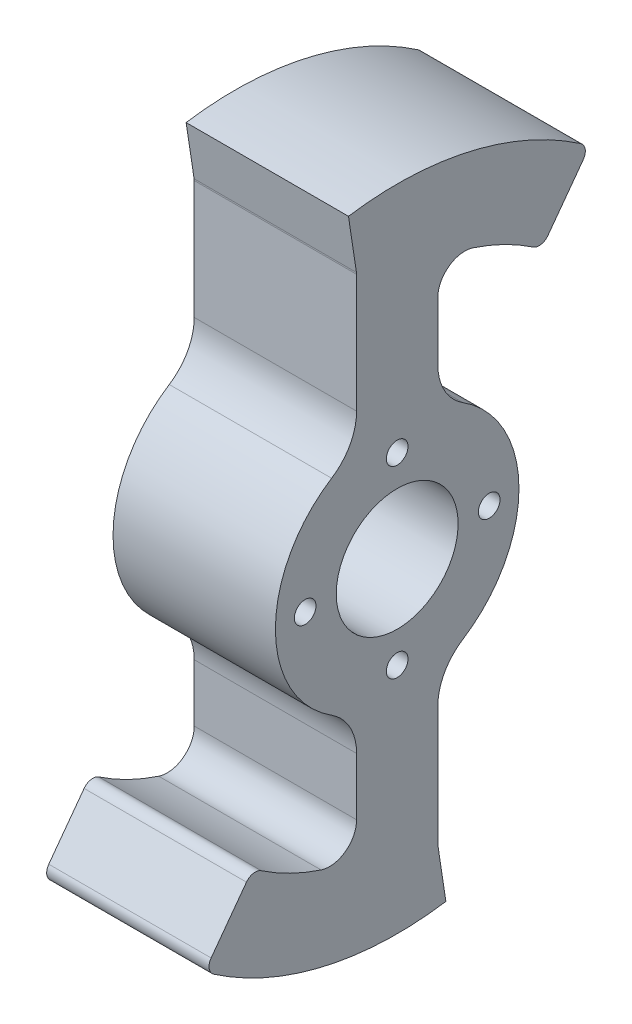
SolidWorks part; units mm, degrees
material "AISI Type A2 Tool Steel"
ref_plane "Front Plane" through (0, 0, 0) normal (0, 0, 1) x (1, 0, 0)
ref_plane "Top Plane" through (0, 0, 0) normal (0, 1, 0) x (1, 0, 0)
ref_plane "Right Plane" through (0, 0, 0) normal (1, 0, 0) x (0, 0, -1)
sketch "Sketch1" plane through (0, 0, 0) normal (1, 0, 0) x (0, 0, -1)
  line L0 (-9.525, 26.9408) -> (-9.525, 62.7816)
  line L1 (-9.525, 62.7816) -> (-11.43, 75.3379)
  line L2 (45.1897, 61.3542) -> (35.3665, 48.0172)
  line L3 (9.525, -26.9408) -> (9.525, -62.7816)
  line L4 (9.525, 48.2558) -> (9.525, 26.9408)
  line L5 (0, 28.575) -> (0, 117.6695) construction
  line L6 (45.1897, 61.3542) -> (134.5364, -4.4531) construction
  line L7 (9.525, -62.7816) -> (11.43, -75.3379)
  line L8 (-45.1897, -61.3542) -> (-35.3665, -48.0172)
  line L9 (-9.525, -48.2558) -> (-9.525, -26.9408)
  line L10 (0, -28.575) -> (0, -117.6695) construction
  line L11 (-45.1897, -61.3542) -> (-134.5364, 4.4531) construction
  circle A0 centre (0, 0) radius 28.575 construction
  circle A1 centre (0, 0) radius 14.3002
  arc A2 (-11.43, 75.3379) -> (45.1897, 61.3542) centre (0, 0) cw
  arc A3 (31.9035, 47.4162) -> (17.8594, 54.2878) centre (0, 0) ccw
  arc A4 (17.8594, 54.2878) -> (9.525, 48.2558) centre (15.875, 48.2558) ccw
  arc A5 (35.3665, 48.0172) -> (31.9035, 47.4162) centre (33.3214, 49.5235) cw
  arc A6 (11.43, -75.3379) -> (-45.1897, -61.3542) centre (0, 0) cw
  arc A7 (-31.9035, -47.4162) -> (-17.8594, -54.2878) centre (0, 0) ccw
  arc A8 (-17.8594, -54.2878) -> (-9.525, -48.2558) centre (-15.875, -48.2558) ccw
  arc A9 (-35.3665, -48.0172) -> (-31.9035, -47.4162) centre (-33.3214, -49.5235) cw
  arc A10 (-9.525, 26.9408) -> (-9.525, -26.9408) centre (0, 0) ccw
  arc A11 (9.525, 26.9408) -> (9.525, -26.9408) centre (0, 0) cw
  circle A12 centre (0, 0) radius 9.525
  point P18 (33.8923, 46.0156)
  point P36 (0, 0)
  dimension "D1" = 57.15
  dimension "D2" = 28.6004
  dimension "D3" = 19.05
  dimension "D4" = 76.2
  dimension "D6" = 45
  dimension "D8" = 6.35
  dimension "D9" = 2.54
  dimension "D11" = 19.05
  dimension "D5" = 12.7
  dimension "D7" = 19.05
  dimension "D10" = 2
extrude "Boss-Extrude1" add sketch "Sketch1" along normal mid plane 38.1 contours A11 L4 A4 A3 A5 L2 A2 L1 L0 A10 L9 A8 A7 A9 L8 A6 L7 L3 A1 region at (0, 44.8612, 7.7532)
fillet "Fillet1" radius 2.54 4 edges at (0, -61.3542, 45.1897) (0, 61.3542, -45.1897) (0, -62.7816, -9.525) (0, 62.7816, 9.525)
fillet "Fillet2" radius 12.7 4 edges at (0, 26.9408, -9.525) (0, -26.9408, -9.525) (0, -26.9408, 9.525) (0, 26.9408, 9.525)
sketch "Sketch2" plane through (-19.05, 0, 0) normal (-1, 0, 0) x (0, 0, 1)
  circle A0 centre (0, 21.59) radius 2.54
  circle A1 centre (21.59, 0) radius 2.54
  circle A2 centre (0, -21.59) radius 2.54
  circle A3 centre (-21.59, 0) radius 2.54
  point P12 (0, 0)
  dimension "D1" = 5.08
  dimension "D2" = 21.59
  dimension "D3" = 4
extrude "Cut-Extrude1" cut sketch "Sketch2" against normal up to next
